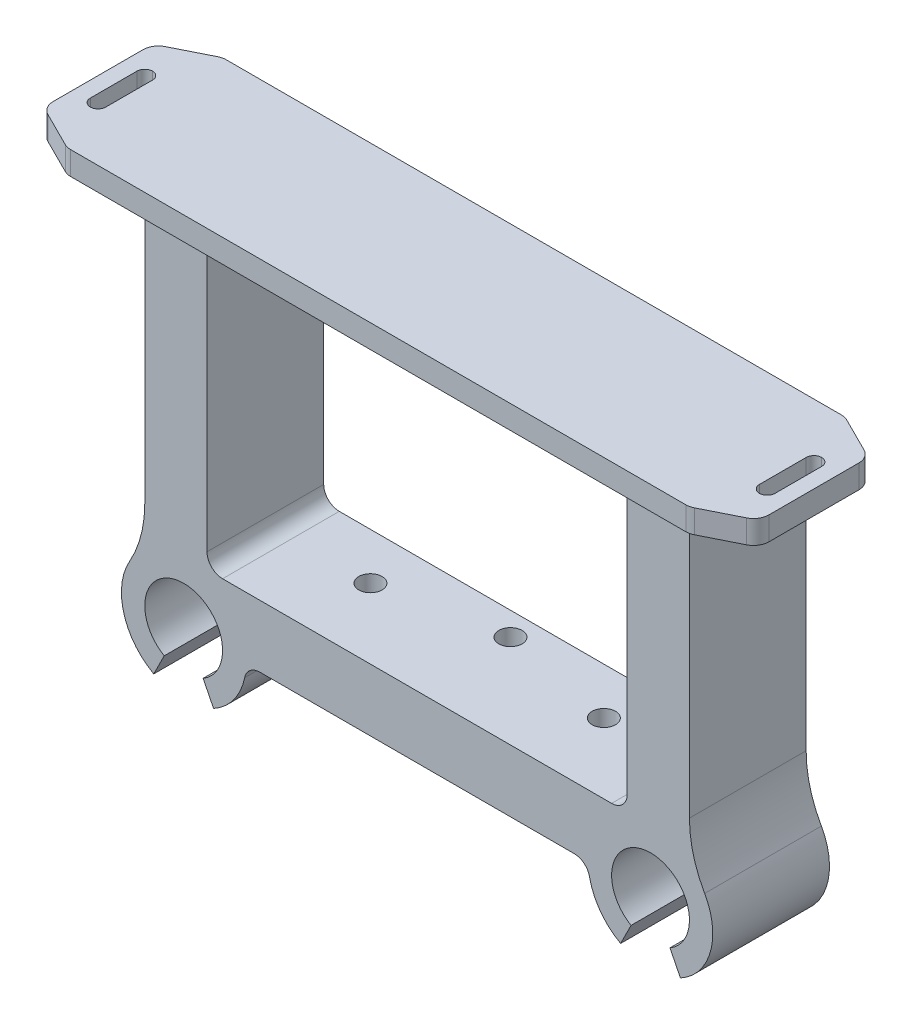
SolidWorks part; units mm, degrees
other "Camera1"
ref_plane "Front Plane" through (0, 0, 0) normal (0, 0, 1) x (1, 0, 0)
ref_plane "Top Plane" through (0, 0, 0) normal (0, 1, 0) x (1, 0, 0)
ref_plane "Right Plane" through (0, 0, 0) normal (1, 0, 0) x (0, 0, -1)
sketch "Sketch1" plane through (0, 0, 0) normal (0, 0, 1) x (1, 0, 0)
  line L1 (-17.9483, -1.6422) -> (52.0517, -1.6422)
  line L2 (-17.9483, -1.6422) -> (-17.9483, -9.6422)
  line L3 (-17.9483, -9.6422) -> (52.0517, -9.6422)
  line L4 (52.0517, -1.6422) -> (52.0517, -9.6422)
  line L5 (-17.9483, -1.6422) -> (-9.9483, -1.6422)
  line L6 (-17.9483, -1.6422) -> (-17.9483, 38.3578)
  line L7 (-17.9483, 38.3578) -> (-9.9483, 38.3578)
  line L8 (-9.9483, -1.6422) -> (-9.9483, 38.3578)
  line L9 (52.0517, -1.6422) -> (44.0517, -1.6422)
  line L10 (52.0517, -1.6422) -> (52.0517, 38.3578)
  line L11 (52.0517, 38.3578) -> (44.0517, 38.3578)
  line L12 (44.0517, -1.6422) -> (44.0517, 38.3578)
  dimension "D1" = 8
  dimension "D2" = 70
  dimension "D3" = 40
  dimension "D4" = 8
  dimension "D5" = 40
  dimension "D6" = 8
  dimension "D7" = 54
  dimension "D8" = 70
extrude "Boss-Extrude1" add sketch "Sketch1" along normal blind 15 contours L1 L8 L7 L6 | L4 L1 L2 L3 | L12 L1 L10 L11 region at (-13.9483, 18.3578, 0) region at (17.0517, -5.6422, 0) region at (48.0517, 18.3578, 0)
sketch "Sketch4" plane through (0, 0, 15) normal (0, 0, 1) x (1, 0, 0)
  line L2 (-17.9483, -9.6422) -> (52.0517, -9.6422) construction
  line L3 (-17.9483, -9.6422) -> (52.0517, -9.6422) construction
  line L4 (-17.9483, -9.6422) -> (-17.9483, 38.3578) construction
  circle A0 centre (-12.9483, -9.6422) radius 8
  circle A1 centre (47.0517, -9.6422) radius 8
  dimension "D1" = 60
  dimension "D2" = 5
  dimension "D3" = 0
  dimension "D4" = 0
extrude "Boss-Extrude2" add sketch "Sketch4" against normal up to surface (15 mm away) up to face at (17.0517, 16.3578, 0)
sketch "Sketch5" plane through (0, 0, 15) normal (0, 0, 1) x (1, 0, 0)
  line L0 (-17.9483, -3.3972) -> (-17.9483, 38.3578) construction
  line L2 (-4.9483, -9.6422) -> (39.0517, -9.6422) construction
  circle A0 centre (-12.9483, -9.6422) radius 5
  circle A1 centre (47.0517, -9.6422) radius 5
  dimension "D5" = 10
  dimension "D6" = 10
  dimension "D1" = 5
  dimension "D2" = 60
  dimension "D3" = 0
  dimension "D4" = 0
extrude "Cut-Extrude2" cut sketch "Sketch5" against normal up to surface (15 mm away) up to face at (17.0517, 10.34, 0)
fillet "Fillet2" radius 15 2 edges at (52.0517, -3.3972, 7.5) (-17.9483, -3.3972, 7.5)
fillet "Fillet3" radius 2 2 edges at (39.0517, -9.6422, 7.5) (-4.9483, -9.6422, 7.5)
fillet "Fillet4" radius 2 2 edges at (44.0517, -1.6422, 7.5) (-9.9483, -1.6422, 7.5)
sketch "Sketch6" plane through (0, 38.3578, 0) normal (0, 1, 0) x (1, 0, 0)
  line L1 (-22.9483, 0) -> (57.0517, 0)
  line L2 (-22.9483, 0) -> (-22.9483, -20)
  line L3 (-22.9483, -20) -> (57.0517, -20)
  line L4 (57.0517, 0) -> (57.0517, -20)
  line L7 (-17.9483, -15) -> (-9.9483, -15) construction
  dimension "D1" = 5
  dimension "D2" = 80
  dimension "D4" = 20
  dimension "D5" = 5
extrude "Boss-Extrude3" add sketch "Sketch6" along normal blind 3
sketch "Sketch10" plane through (0, -1.6422, 0) normal (0, 1, 0) x (1, 0, 0)
  line L3 (-7.9483, 0) -> (42.0517, 0) construction
  circle A0 centre (2.0517, -6) radius 1.5
  circle A1 centre (17.0517, -3) radius 1.5
  circle A2 centre (32.0517, -6) radius 1.5
  dimension "D1" = 15
  dimension "D5" = 3
  dimension "D6" = 3
  dimension "D7" = 3
  dimension "D2" = 6
  dimension "D3" = 12
  dimension "D4" = 6
  dimension "D8" = 3
  dimension "D9" = 15
  dimension "D10" = 12
extrude "Cut-Extrude3" cut sketch "Sketch10" against normal up to next
sketch "Sketch11" plane through (0, 38.3578, 0) normal (0, -1, 0) x (1, 0, 0)
  line L0 (44.0517, 0) -> (-9.9483, 0) construction
  line L1 (24.5517, 0) -> (9.5517, 0)
  line L2 (24.5517, 0) -> (24.5517, 8.3114)
  line L3 (24.5517, 8.3114) -> (9.5517, 8.3114)
  line L4 (9.5517, 0) -> (9.5517, 8.3114)
  point P8 (17.0517, 0)
  dimension "D2" = 15
  dimension "D3" = 27
extrude "Boss-Extrude4" add sketch "Sketch11" along normal blind 10 from surface starting at face at (17.0517, 38.3578, 8.3333)
sketch "Sketch12" plane through (0, 41.3578, 0) normal (0, 1, 0) x (1, 0, 0)
  line L0 (-22.9483, 0) -> (-28.9483, -3)
  line L1 (-28.9483, -3) -> (-28.9483, -17)
  line L2 (-28.9483, -17) -> (-22.9483, -20)
  line L3 (-22.9483, -20) -> (-22.9483, 0)
  line L4 (57.0517, -20) -> (63.0517, -17)
  line L5 (63.0517, -17) -> (63.0517, -3)
  line L6 (63.0517, -3) -> (57.0517, 0)
  line L7 (57.0517, 0) -> (57.0517, -20)
  dimension "D1" = 6
  dimension "D2" = 3
  dimension "D3" = 3
  dimension "D4" = 20
  dimension "D5" = 6
  dimension "D6" = 3
  dimension "D7" = 3
extrude "Boss-Extrude5" add sketch "Sketch12" against normal up to surface (3 mm away) up to face at (17.0517, 38.3578, 7.2889)
sketch "Sketch13" plane through (0, 41.3578, 0) normal (0, 1, 0) x (1, 0, 0)
  line L0 (57.0517, 0) -> (-22.9483, 0) construction
  line L1 (59.0517, -6) -> (61.0517, -6)
  line L2 (59.0517, -6) -> (59.0517, -14)
  line L3 (59.0517, -14) -> (61.0517, -14)
  line L4 (61.0517, -6) -> (61.0517, -14)
  line L5 (-22.9483, -20) -> (57.0517, -20) construction
  line L6 (-26.9483, -6) -> (-24.9483, -6)
  line L7 (-26.9483, -6) -> (-26.9483, -14)
  line L8 (-26.9483, -14) -> (-24.9483, -14)
  line L9 (-24.9483, -6) -> (-24.9483, -14)
  dimension "D1" = 8
  dimension "D2" = 2
  dimension "D3" = 6
  dimension "D4" = 6
  dimension "D5" = 2
  dimension "D6" = 2
  dimension "D7" = 2
  dimension "D8" = 8
  dimension "D9" = 6
extrude "Cut-Extrude5" cut sketch "Sketch13" against normal up to next contours L6 L9 L8 L7 | L2 L1 L4 L3
fillet "Fillet5" radius 1 8 edges at (59.0517, 39.8578, 6) (61.0517, 39.8578, 6) (61.0517, 39.8578, 14) (59.0517, 39.8578, 14) (-26.9483, 39.8578, 14) (-24.9483, 39.8578, 14) (-24.9483, 39.8578, 6) (-26.9483, 39.8578, 6)
fillet "Fillet6" radius 2 8 edges at (57.0517, 39.8578, 20) (63.0517, 39.8578, 17) (63.0517, 39.8578, 3) (57.0517, 39.8578, 0) (-22.9483, 39.8578, 0) (-28.9483, 39.8578, 3) (-22.9483, 39.8578, 20) (-28.9483, 39.8578, 17)
sketch "Sketch14" plane through (0, 0, 0) normal (0, 0, -1) x (-1, 0, 0)
  line L0 (-42.0517, -18.9724) -> (-52.0517, -18.9724)
  line L1 (-52.0517, -18.9724) -> (-49.5517, -13.9724)
  line L2 (-49.5517, -13.9724) -> (-44.5517, -13.9724)
  line L3 (-44.5517, -13.9724) -> (-42.0517, -18.9724)
  line L4 (17.9483, -18.9724) -> (7.9483, -18.9724)
  line L5 (7.9483, -18.9724) -> (10.4483, -13.9724)
  line L6 (10.4483, -13.9724) -> (15.4483, -13.9724)
  line L7 (15.4483, -13.9724) -> (17.9483, -18.9724)
  circle A0 centre (-47.0517, -9.6422) radius 5 construction
  circle A1 centre (12.9483, -9.6422) radius 5 construction
  point P16 (-47.0517, -18.9724)
  point P17 (-47.0517, -13.9724)
  point P18 (12.9483, -18.9724)
  point P19 (12.9483, -13.9724)
  dimension "D1" = 10
  dimension "D2" = 5
  dimension "D3" = 5
  dimension "D4" = 5
  dimension "D5" = 10
  dimension "D6" = 5
extrude "Cut-Extrude6" cut sketch "Sketch14" against normal up to next
sketch "Sketch15" plane through (0, 0, 0) normal (0, 0, -1) x (-1, 0, 0)
  line L1 (-9.5517, 28.3578) -> (-24.5517, 28.3578) construction
  line L8 (-12.4329, 34.3578) -> (-14.7423, 38.3578)
  line L9 (-14.7423, 38.3578) -> (-19.3611, 38.3578)
  line L10 (-19.3611, 38.3578) -> (-21.6705, 34.3578)
  line L11 (-21.6705, 34.3578) -> (-19.3611, 30.3578)
  line L12 (-19.3611, 30.3578) -> (-14.7423, 30.3578)
  line L13 (-14.7423, 30.3578) -> (-12.4329, 34.3578)
  circle A1 centre (-17.0517, 34.3578) radius 4 construction
  point P6 (-17.0517, 28.3578)
  dimension "D1" = 6
  dimension "D2" = 8
fillet "Fillet7" radius 6 2 edges at (9.5517, 28.3578, 4.1557) (24.5517, 28.3578, 4.1557)
fillet "Fillet8" radius 6 2 edges at (24.5517, 38.3578, 4.1557) (9.5517, 38.3578, 4.1557)
fillet "Fillet9" radius 2 1 edges at (17.0517, 38.3578, 8.3114)
extrude "Cut-Extrude7" cut sketch "Sketch15" against normal blind 15
fillet "Fillet10" radius 2 6 edges at (-13.9483, 38.3578, 15) (48.0517, 38.3578, 15) (52.0517, 38.3578, 7.5) (44.0517, 38.3578, 7.5) (-9.9483, 38.3578, 7.5) (-17.9483, 38.3578, 7.5)
